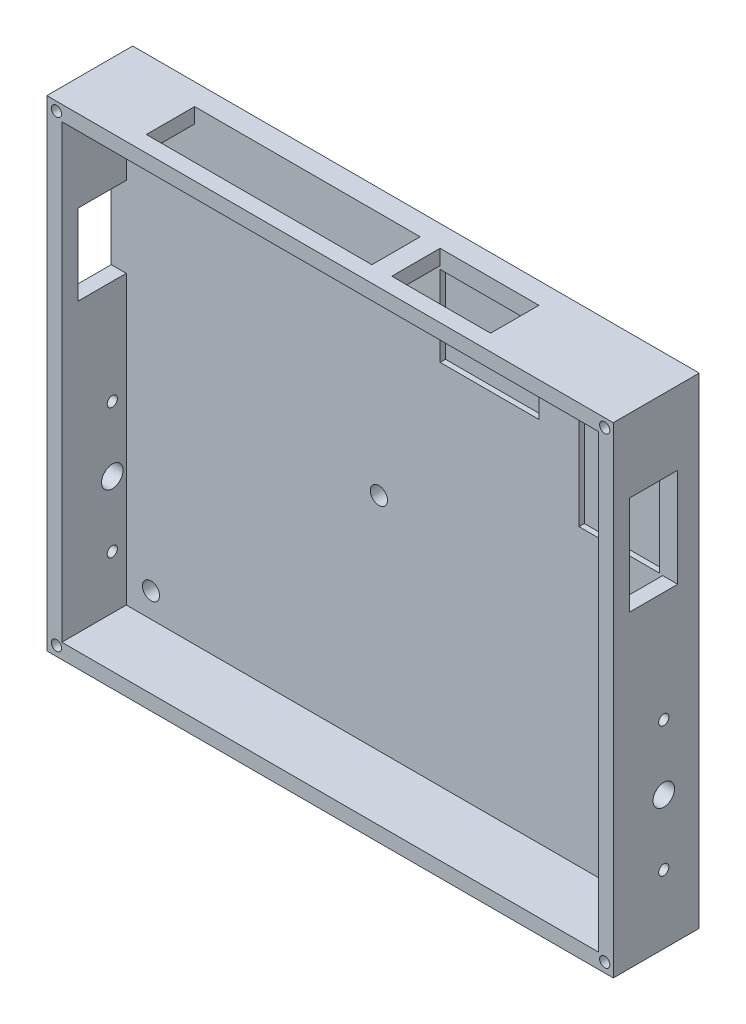
SolidWorks part; units mm, degrees
material "6061 合金"
ref_plane "前视基准面" through (0, 0, 0) normal (0, 0, 1) x (1, 0, 0)
ref_plane "上视基准面" through (0, 0, 0) normal (0, 1, 0) x (1, 0, 0)
ref_plane "右视基准面" through (0, 0, 0) normal (1, 0, 0) x (0, 0, -1)
other "Configuration Table"
sketch "草图3" plane through (0, 0, 0) normal (0, 0, 1) x (1, 0, 0)
  line L0 (-1.7, -1.7) -> (-1.7, 43.08)
  line L1 (0, 0) -> (49.35, 0)
  line L2 (0, 0) -> (0, 41.38)
  line L3 (0, 41.38) -> (49.35, 41.38)
  line L4 (49.35, 0) -> (49.35, 41.38)
  line L5 (-1.7, 43.08) -> (51.05, 43.08)
  line L6 (51.05, -1.7) -> (51.05, 43.08)
  line L7 (-1.7, -1.7) -> (51.05, -1.7)
  line L8 (28.923, 41.38) -> (28.923, 33.88)
  line L9 (28.923, 33.88) -> (38.123, 33.88)
  line L10 (38.123, 33.88) -> (38.123, 41.38)
  line L11 (49.35, 36.3) -> (41.85, 36.3)
  line L12 (41.85, 36.3) -> (41.85, 27.1)
  line L13 (41.85, 27.1) -> (49.35, 27.1)
  line L14 (28.923, 41.38) -> (38.123, 41.38)
  line L15 (49.35, 36.3) -> (49.35, 27.1)
  line L16 (-0.3, -0.3) -> (-0.3, 41.68)
  line L17 (-0.3, 41.68) -> (49.65, 41.68)
  line L18 (49.65, -0.3) -> (49.65, 41.68)
  line L19 (-0.3, -0.3) -> (49.65, -0.3)
  dimension "D1" = 49.35
  dimension "D2" = 41.38
  dimension "D4" = 9.2
  dimension "D5" = 7.5
  dimension "D6" = 9.2
  dimension "D7" = 7.5
  dimension "D8" = 0.3
  dimension "D3" = 1.7
extrude "凸台-拉伸1" add sketch "草图3" along normal blind 2 contours L5 L6 L7 L0
hole_wizard "M2 螺纹孔1" positions "3D草图2" profile "草图4" tap size "M2" standard "GB" end condition through all
sketch3d "3D草图2"
  point P0 (2.003, 2, 2)
  point P2 (47.45, 2, 2)
  point P4 (47.45, 39.357, 2)
  point P6 (2.003, 39.357, 2)
  point P16 (23.225, 20.3, 2)
sketch "草图4" plane through (2.003, 2, 2) normal (1, 0, 0) x (0, -1, 0)
  line L0 (0, 0) -> (0, 2)
  line L1 (0, 2) -> (0.8, 2)
  line L2 (0.8, 2) -> (0.8, 0)
  line L5 (0.8, 0) -> (0, 0)
  line L11 (0, -6.35) -> (0, 107.95) construction
  dimension "通孔螺纹孔钻头直径" = 1.6
  dimension "通孔螺纹孔钻头深度" = 2
cosmetic thread "孔螺纹线1" parameters "D2"=2
cosmetic thread "孔螺纹线2" parameters "D2"=2
cosmetic thread "孔螺纹线3" parameters "D2"=2
cosmetic thread "孔螺纹线4" parameters "D2"=2
cosmetic thread "孔螺纹线5" parameters "D2"=2
extrude "切除-拉伸2" cut sketch "草图3<5>" against normal blind 0.5 from surface contours L9 L10 L3 L8 | L12 L13 L15 L11 region at (33.523, 37.63, 0) starting at face at (2.803, 2, 2)
sketch "草图3<5>" plane through (0, 0, 0) normal (0, 0, 1) x (1, 0, 0) same geometry as "草图3"
extrude "凸台-拉伸3" add sketch "草图3<6>" along normal blind 8 contours L16 L17 L18 L19 | L0 L5 L6 L7
sketch "草图3<6>" plane through (0, 0, 0) normal (0, 0, 1) x (1, 0, 0) same geometry as "草图3"
sketch "草图10" plane through (-1.7, 0, 0) normal (-1, 0, 0) x (0, 0, 1)
  circle A0 centre (3.3, 10.725) radius 1
  point P2 (0, 0)
extrude "切除-拉伸5" cut sketch "草图10" against normal through all contours A0
hole_wizard "M1.2x0.25 螺纹孔1" positions "草图11" profile "草图12" tap size "M1.2x0.25" standard "GB" end condition through all
sketch "草图11" plane through (-1.7, 0, 0) normal (-1, 0, 0) x (0, 0, 1)
  point P0 (3.3, 16.775)
  point P2 (3.3, 4.675)
sketch "草图12" plane through (-1.7, 16.775, 3.3) normal (0, 1, 0) x (0, 0, 1)
  line L0 (0, 0) -> (0, 52.75)
  line L1 (0, 52.75) -> (0.475, 52.75)
  line L2 (0.475, 52.75) -> (0.475, 0)
  line L5 (0.475, 0) -> (0, 0)
  line L11 (0, -6.35) -> (0, 107.95) construction
  dimension "通孔螺纹孔钻头直径" = 0.95
  dimension "通孔螺纹孔钻头深度" = 52.75
cosmetic thread "孔螺纹线6" parameters "D2"=1.2
cosmetic thread "孔螺纹线7" parameters "D2"=1.2
sketch "草图13" plane through (51.05, 0, 0) normal (1, 0, 0) x (0, 0, -1)
  line L1 (-6.5, 36.25) -> (-2, 36.25)
  line L2 (-6.5, 36.25) -> (-6.5, 27.05)
  line L3 (-6.5, 27.05) -> (-2, 27.05)
  line L4 (-2, 36.25) -> (-2, 27.05)
  line L5 (-2, 36.3) -> (-2, 27.1) construction
  dimension "D1" = 4.5
extrude "切除-拉伸6" cut sketch "草图13" against normal blind 2
sketch "草图14" plane through (0, 43.08, 0) normal (0, 1, 0) x (1, 0, 0)
  line L0 (28.923, -2) -> (38.123, -2) construction
  line L1 (28.923, -2) -> (38.123, -2)
  line L2 (28.923, -2) -> (28.923, -6.5)
  line L3 (28.923, -6.5) -> (38.123, -6.5)
  line L4 (38.123, -2) -> (38.123, -6.5)
  line L7 (6.07, -2) -> (27.07, -2)
  line L8 (6.07, -2) -> (6.07, -6.5)
  line L9 (6.07, -6.5) -> (27.07, -6.5)
  line L10 (27.07, -2) -> (27.07, -6.5)
  dimension "D1" = 4.5
  dimension "D2" = 0
  dimension "D3" = 4.5
extrude "切除-拉伸7" cut sketch "草图14" against normal blind 2
sketch "草图15" plane through (-1.7, 0, 0) normal (-1, 0, 0) x (0, 0, 1)
  line L1 (2, 33.95) -> (6.5, 33.95)
  line L2 (2, 33.95) -> (2, 26.45)
  line L3 (2, 26.45) -> (6.5, 26.45)
  line L4 (6.5, 33.95) -> (6.5, 26.45)
extrude "切除-拉伸8" cut sketch "草图15" against normal blind 2
hole_wizard "M1.2x0.25 螺纹孔2" positions "3D草图3" profile "草图16" tap size "M1.2x0.25" standard "GB" end condition through all
sketch3d "3D草图3"
  point P0 (-0.8, -0.8, 8)
  point P2 (50.25, -0.8, 8)
  point P4 (50.25, 42.28, 8)
  point P6 (-0.8, 42.28, 8)
sketch "草图16" plane through (-0.8, -0.8, 8) normal (1, 0, 0) x (0, -1, 0)
  line L0 (0, 0) -> (0, 8)
  line L1 (0, 8) -> (0.475, 8)
  line L2 (0.475, 8) -> (0.475, 0)
  line L5 (0.475, 0) -> (0, 0)
  line L11 (0, -6.35) -> (0, 107.95) construction
  dimension "通孔螺纹孔钻头直径" = 0.95
  dimension "通孔螺纹孔钻头深度" = 8
cosmetic thread "孔螺纹线8" parameters "D2"=1.2
cosmetic thread "孔螺纹线9" parameters "D2"=1.2
cosmetic thread "孔螺纹线10" parameters "D2"=1.2
cosmetic thread "孔螺纹线11" parameters "D2"=1.2
